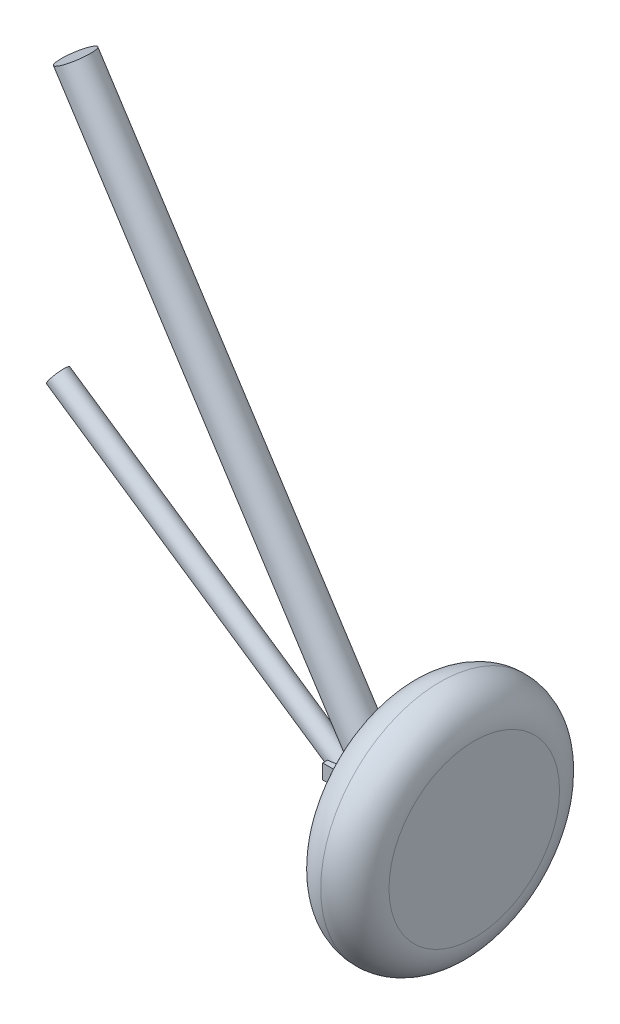
SolidWorks part; units mm, degrees
ref_plane "Ön Düzlem" through (0, 0, 0) normal (0, 0, 1) x (1, 0, 0)
ref_plane "Üst Düzlem" through (0, 0, 0) normal (0, 1, 0) x (1, 0, 0)
ref_plane "Sağ Düzlem" through (0, 0, 0) normal (1, 0, 0) x (0, 0, -1)
sketch "Çizim1" plane through (0, 0, 0) normal (1, 0, 0) x (0, 0, -1)
  circle A0 centre (0, 0) radius 3.5
  dimension "D1" = 7
extrude "Yükseklik-Ekstrüzyon1" add sketch "Çizim1" along normal blind 1 and the other way blind 1
fillet "Radyus1" radius 1 1 edges at (1, 0, -3.5) type face fillet first side face at (1, 0, -3.5) second side face at (-1, 0, -3.5)
fillet "Radyus2" radius 1 1 edges at (-1, 0, -3.5) type face fillet first side face at (0, 0, -3.5) second side face at (-1, 0, -3.5)
sketch "Çizim2" plane through (-1, 0, 0) normal (-1, 0, 0) x (0, 0, 1)
  line L1 (-0.4232, 0.1621) -> (0.4412, 0.1621)
  line L2 (-0.4232, 0.1621) -> (-0.4232, -0.2701)
  line L3 (-0.4232, -0.2701) -> (0.4412, -0.2701)
  line L4 (0.4412, 0.1621) -> (0.4412, -0.2701)
extrude "Yükseklik-Ekstrüzyon2" add sketch "Çizim2" along normal blind 2
sketch "Çizim3" plane through (0, 0, 0) normal (0, 0, 1) x (1, 0, 0)
  line L0 (-1.6147, 0) -> (-10.6853, 14.0423)
revolve "Döndür-İnce1" add sketch "Çizim3" angle 360 about L0 wall 0.5
sketch "Çizim4" plane through (0, 0, 0) normal (0, 0, 1) x (1, 0, 0)
  line L0 (-2.8105, 0) -> (-11.1994, 5.6864)
revolve "Döndür-İnce2" add sketch "Çizim4" angle 360 about L0 wall 0.3
